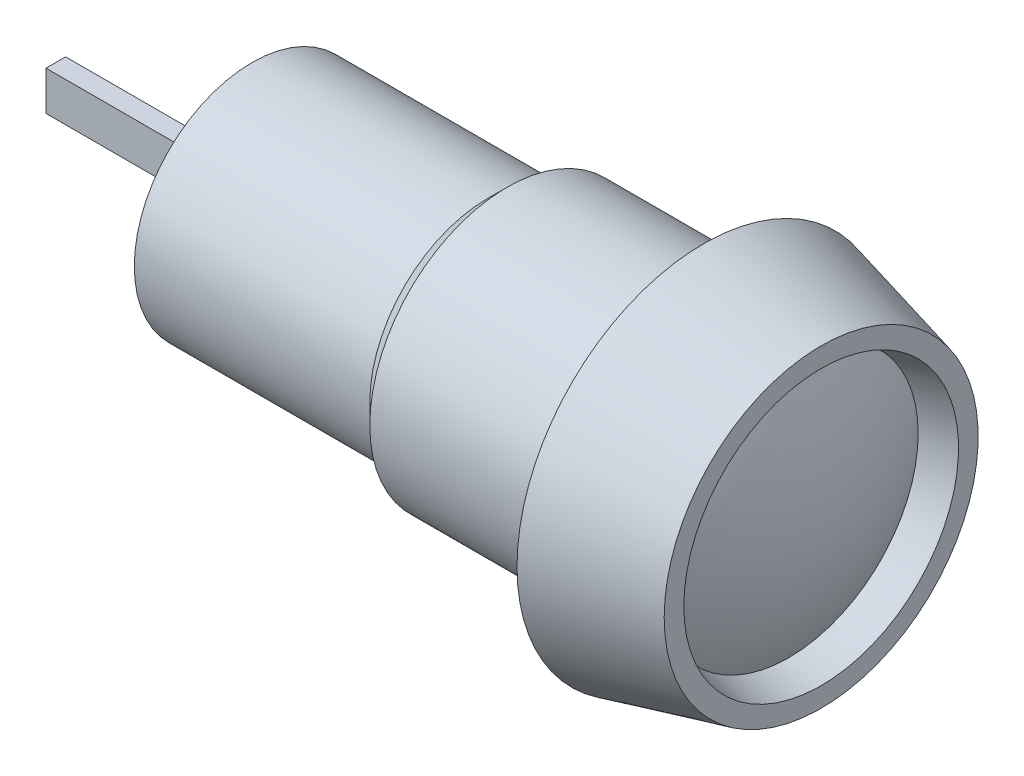
SolidWorks part; units mm, degrees
ref_plane "Front Plane" through (0, 0, 0) normal (0, 0, 1) x (1, 0, 0)
ref_plane "Top Plane" through (0, 0, 0) normal (0, 1, 0) x (1, 0, 0)
ref_plane "Right Plane" through (0, 0, 0) normal (1, 0, 0) x (0, 0, -1)
sketch "Sketch1" plane through (0, 0, 0) normal (0, 1, 0) x (1, 0, 0)
  line L0 (0, 0) -> (-23, 0) construction
  line L1 (0, 0) -> (6, 0) construction
  line L2 (6, 7) -> (6, 8)
  line L3 (6, 8) -> (0, 9.5)
  line L4 (0, 9.5) -> (0, 7)
  line L5 (0, 7) -> (-10, 7)
  line L6 (-10, 7) -> (-11, 6)
  line L7 (-11, 6) -> (-23, 6)
  line L8 (-23, 6) -> (-23, 0)
  line L9 (-23, 0) -> (6, 0)
  line L10 (6, 7) -> (4.3529, 6.5882)
  line L11 (6, 7.5) -> (0, 7.5) construction
  arc A0 (4.3529, 6.5882) -> (6, 0) centre (-8, 0) cw
  point P13 (4.3381, 6.5845)
  point P14 (6.1824, 7)
  dimension "D9" = 1
  dimension "D10" = 14
  dimension "D1" = 23
  dimension "D2" = 6
  dimension "D3" = 14
  dimension "D4" = 16
  dimension "D5" = 19
  dimension "D6" = 12
  dimension "D7" = 11
  dimension "D8" = 45
revolve "Revolve1" add sketch "Sketch1" angle 360 about L9
sketch "Sketch3" plane through (0, 0, 0) normal (0, 0, 1) x (1, 0, 0)
  line L0 (-23, 6) -> (-23, -6) construction
  line L1 (-23, 1) -> (-33, 1)
  line L2 (-23, 1) -> (-23, -1)
  line L3 (-23, -1) -> (-33, -1)
  line L4 (-33, 1) -> (-33, -1)
  line L5 (0, 7) -> (0, -7) construction
  point P6 (-23, 0)
  dimension "D1" = 2
  dimension "D2" = 33
extrude "Boss-Extrude1" add sketch "Sketch3" along normal mid plane 1
